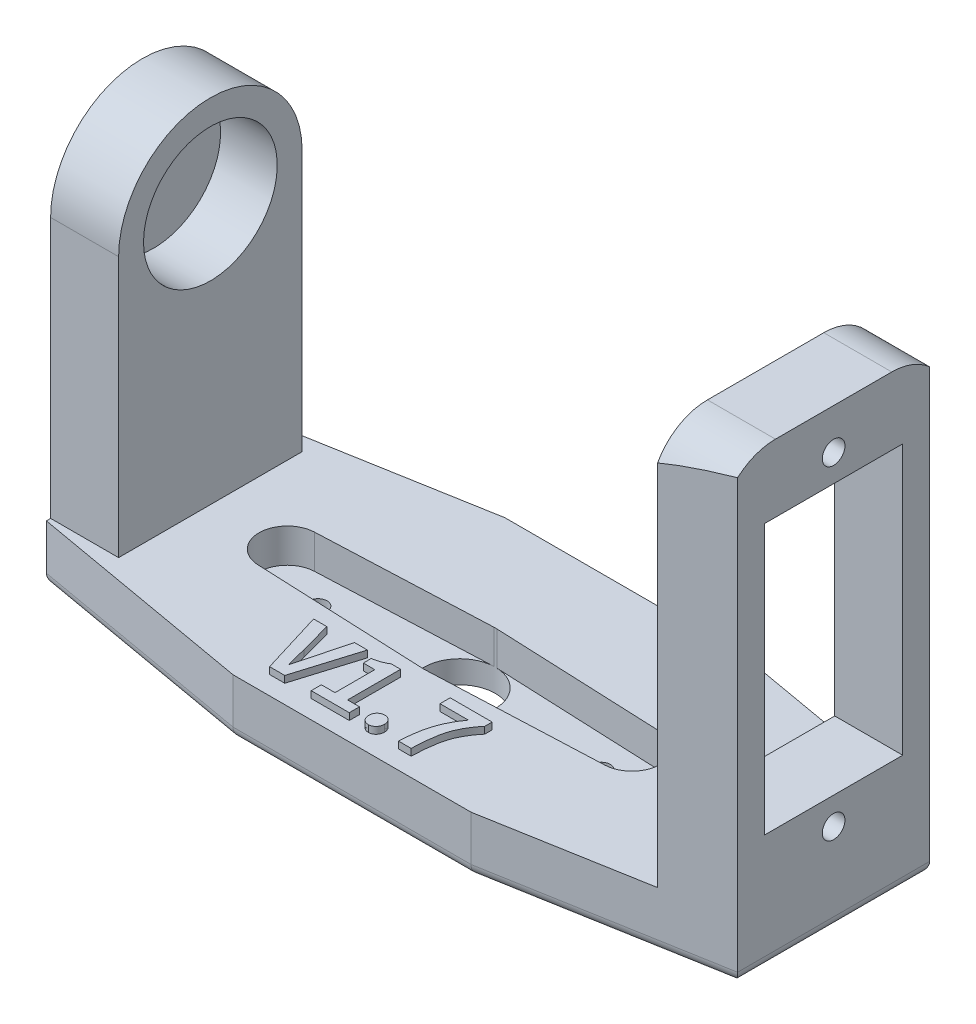
SolidWorks part; units mm, degrees
ref_plane "前视基准面" through (0, 0, 0) normal (0, 0, 1) x (1, 0, 0)
ref_plane "上视基准面" through (0, 0, 0) normal (0, 1, 0) x (1, 0, 0)
ref_plane "右视基准面" through (0, 0, 0) normal (1, 0, 0) x (0, 0, -1)
sketch "草图1" plane through (0, 0, 0) normal (0, 1, 0) x (1, 0, 0)
  line L0 (0, 0) -> (2.5, 0) construction
  line L1 (33, -12) -> (-28, -12)
  line L2 (33, -12) -> (33, 12)
  line L3 (33, 12) -> (-28, 12)
  line L4 (-28, -12) -> (-28, 12)
  line L5 (33, -12) -> (-28, 12) construction
  line L6 (33, 12) -> (-28, -12) construction
  point P0 (0, 0)
  dimension "D1" = 28
  dimension "D2" = 33
  dimension "D3" = 24
extrude "凸台-拉伸1" add sketch "草图1" along normal blind 5
sketch "草图2" plane through (-28, 0, 0) normal (-1, 0, 0) x (0, 0, 1)
  line L0 (-12, 5) -> (12, 5) construction
  line L1 (8.0991, 36.0991) -> (-8.0991, 36.0991)
  line L2 (8.0991, 36.0991) -> (8.0991, 5)
  line L3 (8.0991, 5) -> (-8.0991, 5)
  line L4 (-8.0991, 36.0991) -> (-8.0991, 5)
  line L5 (8.0991, 36.0991) -> (-8.0991, 5) construction
  line L6 (8.0991, 5) -> (-8.0991, 36.0991) construction
  line L7 (0, 20.5496) -> (0, 5) construction
  circle A0 centre (0, 28) radius 5.9
  circle A1 centre (0, 28) radius 8.0991 construction
  point P0 (0, 20.5496)
  dimension "D2" = 11.8
  dimension "D1" = 23
extrude "凸台-拉伸2" add sketch "草图2" against normal blind 6
sketch "草图8" plane through (-28, 0, 0) normal (-1, 0, 0) x (0, 0, 1)
  circle A1 centre (0, 28) radius 5.9 construction
  circle A2 centre (0, 28) radius 5.9
extrude "凸台-拉伸4" add sketch "草图8" against normal blind 1
fillet "圆角1" 2 edges at (-25, 36.0991, -8.0991) (-25, 36.0991, 8.0991) type full round first side face at (-25, 20.5496, -8.0991) second side face at (-25, 20.5496, 8.0991) middle face at (-25, 36.0991, 0)
sketch "草图3" plane through (33, 0, 0) normal (1, 0, 0) x (0, 0, -1)
  line L0 (0, 22.2) -> (18.2252, 22.2) construction
  line L1 (10.134, 40.0752) -> (-10.134, 40.0752)
  line L2 (10.134, 40.0752) -> (10.134, 5)
  line L3 (10.134, 5) -> (-10.134, 5)
  line L4 (-10.134, 40.0752) -> (-10.134, 5)
  line L5 (10.134, 40.0752) -> (-10.134, 5) construction
  line L6 (10.134, 5) -> (-10.134, 40.0752) construction
  line L7 (0, 22.2) -> (0, 0) construction
  line L8 (6.1, 34.1) -> (-6.1, 34.1)
  line L9 (6.1, 34.1) -> (6.1, 10.3)
  line L10 (6.1, 10.3) -> (-6.1, 10.3)
  line L11 (-6.1, 34.1) -> (-6.1, 10.3)
  line L12 (6.1, 34.1) -> (-6.1, 10.3) construction
  line L13 (6.1, 10.3) -> (-6.1, 34.1) construction
  line L17 (-12, 5) -> (12, 5) construction
  circle A0 centre (0, 28) radius 5.9 construction
  circle A1 centre (0, 28) radius 5.9 construction
  circle A2 centre (0, 7.9) radius 1
  circle A3 centre (0, 36.5) radius 1
  circle A4 centre (0, 28) radius 6.1 construction
  point P0 (0, 22.5376)
  point P7 (0, 22.2)
  dimension "D5" = 2
  dimension "D1" = 23.8
  dimension "D2" = 12.2
  dimension "D4" = 14.3
extrude "凸台-拉伸3" add sketch "草图3" against normal blind 6
fillet "圆角2" radius 5 2 edges at (30, 40.0752, 10.134) (30, 40.0752, -10.134)
chamfer "倒角1" distance 20 angle 10 4 edges at (33, 2.5, -12) (33, 2.5, 12) (-28, 2.5, 12) (-28, 2.5, -12) first distance on face at (2.5, 2.5, -12) first distance on face at (2.5, 2.5, 12)
fillet "圆角4" radius 1 8 edges at (-18, 0, -10.2367) (-28, 0, 0) (-18, 0, 10.2367) (2.5, 0, 12) (23, 0, 10.2367) (33, 0, 0) (23, 0, -10.2367) (2.5, 0, -12)
sketch "草图4" plane through (-24, 5, 6) normal (0, -1, 0) x (-1, 0, 0)
  line L0 (-24, 6) -> (-8.7944, 6) construction
  line L1 (-8.6961, 3.7021) -> (-23.8739, 3.0527) construction
  line L2 (-23.8739, 8.9473) -> (-8.6961, 8.2979) construction
  line L3 (-23.8653, 9.1471) -> (-8.6876, 8.4977)
  line L4 (-8.6876, 3.5023) -> (-23.8653, 2.8529)
  arc A0 (-23.8739, 8.9473) -> (-23.8739, 3.0527) centre (-24, 6) ccw construction
  arc A1 (-8.6961, 3.7021) -> (-8.6961, 8.2979) centre (-8.7944, 6) ccw construction
  arc A2 (-8.6876, 3.5023) -> (-8.6876, 8.4977) centre (-8.7944, 6) ccw
  arc A3 (-23.8653, 9.1471) -> (-23.8653, 2.8529) centre (-24, 6) ccw
  dimension "D1" = 5.9
  dimension "D2" = 4.6
  dimension "D3" = 4.9
  dimension "D5" = 0.2
extrude "切除-拉伸1" cut sketch "草图4" along normal blind 3
mirror "镜向1" about plane through (0, 0, 0) normal (1, 0, 0) of "切除-拉伸1"
sketch "草图5" plane through (0, 2, 0) normal (0, 1, 0) x (1, 0, 0)
  line L0 (-12.5, 0) -> (0, 0) construction
  line L1 (0, 0) -> (0, 5.837) construction
  arc A1 (-0.1347, -3.1471) -> (0.1347, -3.1471) centre (0, 0) ccw construction
  arc A2 (0.1347, 3.1471) -> (-0.1347, 3.1471) centre (0, 0) ccw construction
  arc A3 (-0.1347, -3.1471) -> (0.1347, -3.1471) centre (0, 0) ccw construction
  arc A4 (0.1347, 3.1471) -> (-0.1347, 3.1471) centre (0, 0) ccw construction
  circle A5 centre (0, 0) radius 3.15
  circle A6 centre (-12.5, 0) radius 0.8
  circle A7 centre (12.5, 0) radius 0.8
  dimension "D2" = 1.6
  dimension "D1" = 12.5
extrude "切除-拉伸2" cut sketch "草图5" against normal blind 2.4
sketch "草图10" plane through (0, 5, 0) normal (0, 1, 0) x (1, 0, 0)
  line L0 (-11.9016, -10.3725) -> (11.9016, -10.3725) construction
  line L1 (0, 0) -> (0, -10.3725) construction
  text T0 "V1.7" font "思源黑体" height in points 18
extrude "凸台-拉伸5" add sketch "草图10" along normal blind 0.6
